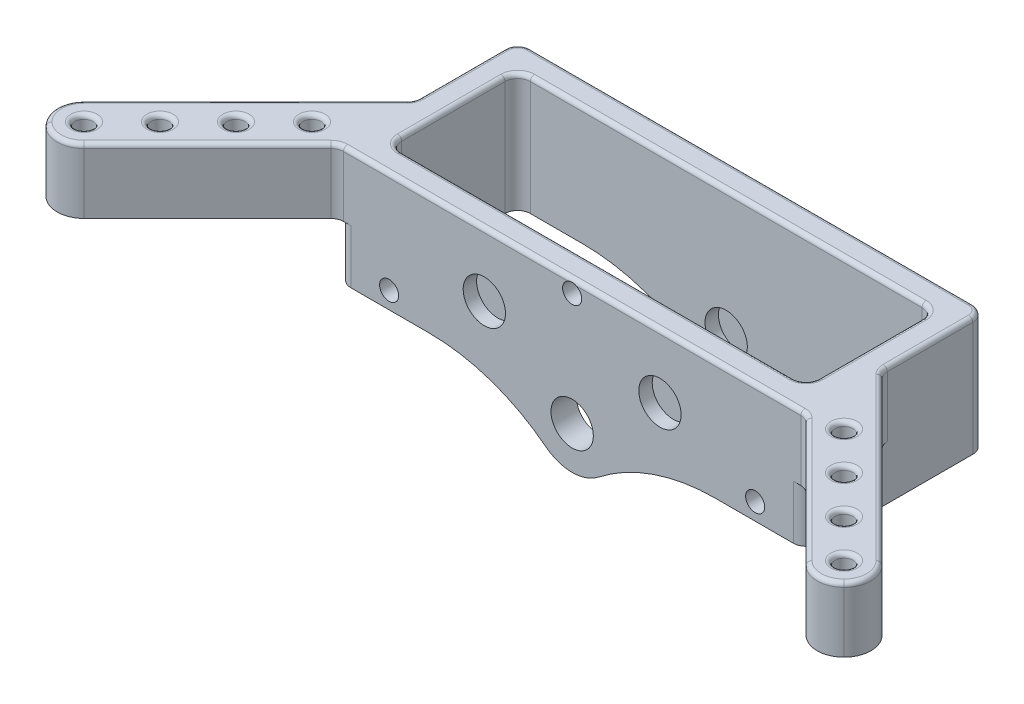
SolidWorks part; units mm, degrees
note: The reader was unsure of these and kept them because the rebuilt part matched: shared geometry of "Sketch4<3>", "Sketch4<5>", "Sketch4<6>", "Sketch4<7>", "Sketch2<4>".
ref_plane "Front Plane" through (0, 0, 0) normal (0, 0, 1) x (1, 0, 0)
ref_plane "Top Plane" through (0, 0, 0) normal (0, 1, 0) x (1, 0, 0)
ref_plane "Right Plane" through (0, 0, 0) normal (1, 0, 0) x (0, 0, -1)
sketch "Sketch2" plane through (0, 0, 0) normal (0, 1, 0) x (1, 0, 0)
  line L0 (-55.275, -21.7) -> (-89.8026, -56.2276)
  line L1 (41.275, 12.7) -> (-41.275, 12.7)
  line L2 (41.275, 12.7) -> (41.275, -12.7)
  line L3 (41.275, -12.7) -> (-41.275, -12.7)
  line L4 (-41.275, 12.7) -> (-41.275, -12.7)
  line L5 (41.275, 12.7) -> (-41.275, -12.7) construction
  line L6 (41.275, -12.7) -> (-41.275, 12.7) construction
  line L7 (-49.275, 14.7) -> (49.275, 14.7)
  line L8 (-49.275, 14.7) -> (-49.275, -15.7)
  line L9 (-49.275, -15.7) -> (49.275, -15.7)
  line L10 (49.275, 14.7) -> (49.275, -15.7)
  line L15 (-55.275, 20.7) -> (55.275, 20.7)
  line L16 (-55.275, 20.7) -> (-55.275, -21.7)
  line L17 (-55.275, -21.7) -> (55.275, -21.7)
  line L18 (55.275, 20.7) -> (55.275, -21.7)
  line L19 (-89.8026, -56.2276) -> (-98.7828, -47.2473)
  line L20 (-98.7828, -47.2473) -> (-55.275, -3.7395)
  line L21 (55.275, -21.7) -> (89.8026, -56.2276)
  line L22 (89.8026, -56.2276) -> (98.7828, -47.2473)
  line L23 (98.7828, -47.2473) -> (55.275, -3.7395)
  line L24 (-96.9319, -54.3766) -> (6.1457, 48.7009) construction
  line L25 (97.4064, -54.8512) -> (0, 42.5553) construction
  circle A0 centre (-89.8026, -47.2473) radius 2.1
  circle A1 centre (-71.842, -29.2868) radius 2.1
  circle A2 centre (71.842, -29.2868) radius 2.1
  circle A3 centre (89.8026, -47.2473) radius 2.1
  circle A4 centre (-62.8618, -20.3065) radius 2.1
  circle A5 centre (-80.8223, -38.267) radius 2.1
  circle A6 centre (62.8618, -20.3065) radius 2.1
  circle A7 centre (80.8223, -38.267) radius 2.1
  point P0 (0, 0)
  point P23 (0, 42.5553)
  dimension "D18" = 4.2
  dimension "D1" = 82.55
  dimension "D2" = 25.4
  dimension "D3" = 6
  dimension "D4" = 6
  dimension "D5" = 6
  dimension "D6" = 8
  dimension "D7" = 8
  dimension "D8" = 2
  dimension "D9" = 3
  dimension "D10" = 6
  dimension "D11" = 12.7
  dimension "D12" = 12.7
  dimension "D13" = 45
  dimension "D14" = 101.6
  dimension "D15" = 25.4
  dimension "D16" = 101.6
  dimension "D17" = 25.4
  dimension "D19" = 6.35
  dimension "D20" = 6.35
  dimension "D21" = 25.4
  dimension "D22" = 25.4
  dimension "D23" = 12.7
  dimension "D24" = 12.7
extrude "Boss-Extrude1" add sketch "Sketch2" along normal blind 28 contours L18 L15 L16 L17 L7 L10 L9 L8 | L20 L19 L0 L16 A1 A0 | L22 L23 L18 L21 A3 A2
sketch "Sketch3" plane through (0, 0, -20.7) normal (0, 0, -1) x (-1, 0, 0)
  line L2 (55.275, 28) -> (-55.275, 28) construction
  circle A0 centre (-43.25, 4) radius 2.25
  circle A1 centre (0, 25) radius 2.25
  circle A2 centre (43.25, 4) radius 2.25
  dimension "D1" = 4.5
  dimension "D2" = 21
  dimension "D3" = 3
  dimension "D4" = 86.5
  dimension "D5" = 43.25
extrude "Cut-Extrude1" cut sketch "Sketch3" against normal up to next from surface
sketch "Sketch4" plane through (0, 0, -20.7) normal (0, 0, -1) x (-1, 0, 0)
  line L0 (55.275, 0) -> (-55.275, 0) construction
  line L1 (55.275, 0) -> (-55.275, 0)
  circle A0 centre (0, 25) radius 2.25 construction
  circle A1 centre (43.25, 4) radius 2.25 construction
  circle A2 centre (-43.25, 4) radius 2.25 construction
  circle A3 centre (0, 25) radius 2.25 construction
  circle A4 centre (43.25, 4) radius 2.25 construction
  circle A5 centre (-43.25, 4) radius 2.25 construction
  circle A6 centre (-20.75, 13) radius 19.05 construction
  circle A7 centre (20.75, 13) radius 19.05 construction
  circle A8 centre (0, -1.6491) radius 6.35 construction
  circle A9 centre (-20.75, 13) radius 5
  circle A10 centre (20.75, 13) radius 5
  circle A11 centre (0, -1.6491) radius 5
  circle A12 centre (0, -1.6491) radius 10
  circle A13 centre (33.8482, -45) radius 45
  circle A14 centre (-33.8482, -45) radius 45
  circle A15 centre (0, -1.6491) radius 7.5
  line M3 (-55.275, 0) -> (55.275, 0)
  dimension "D1" = 38.1
  dimension "D2" = 38.1
  dimension "D3" = 12.7
  dimension "D8" = 10
  dimension "D9" = 10
  dimension "D10" = 10
  dimension "D11" = 20
  dimension "D12" = 90
  dimension "D13" = 15
  dimension "D4" = 9
  dimension "D5" = 9
  dimension "D6" = 22.5
  dimension "D7" = 22.5
extrude "Boss-Extrude2" add sketch "Sketch4" against normal up to surface (6 mm away) contours A14 A12 L1 | L1 A12 A11 M3 | A13 L1 A12 | L1 A11 | A15 A11 M3
extrude "Boss-Extrude3" add sketch "Sketch4<3>" against normal up to surface (6 mm away) from surface
sketch "Sketch4<3>" plane through (0, 0, -20.7) normal (0, 0, -1) x (-1, 0, 0) same geometry as "Sketch4"
extrude "Cut-Extrude3" cut sketch "Sketch4<5>" along normal blind 3.175 from surface at -6 contours L1 A11 | L1 A11 starting at face at (0, 4.9315, -14.7)
sketch "Sketch4<5>" plane through (0, 0, -20.7) normal (0, 0, -1) x (-1, 0, 0) same geometry as "Sketch4"
extrude "Cut-Extrude4" cut sketch "Sketch4<6>" against normal up to next from surface contours L1 A11 | L1 A11
sketch "Sketch4<6>" plane through (0, 0, -20.7) normal (0, 0, -1) x (-1, 0, 0) same geometry as "Sketch4"
fillet "Fillet2" radius 6.35 4 edges at (98.7828, 14, 47.2473) (89.8026, 14, 56.2276) (-89.8026, 14, 56.2276) (-98.7828, 14, 47.2473)
extrude "Cut-Extrude5" cut sketch "Sketch4<7>" along normal blind 3.175 from surface at -42.4 contours A9 | A10 starting at face at (-5, -1.6491, 21.7)
sketch "Sketch4<7>" plane through (0, 0, -20.7) normal (0, 0, -1) x (-1, 0, 0) same geometry as "Sketch4"
extrude "Cut-Extrude6" cut sketch "Sketch2<4>" along normal blind 12.7 contours L20 L19 L0 L16 A5 A4 A1 A0 | L22 L23 L18 L21 A7 A6 A3 A2
sketch "Sketch2<4>" plane through (0, 0, 0) normal (0, 1, 0) x (1, 0, 0) same geometry as "Sketch2"
fillet "Fillet1" radius 3 8 edges at (49.275, 14, 15.7) (-49.275, 14, 15.7) (55.275, 14, -20.7) (49.275, 14, -14.7) (-49.275, 14, -14.7) (-55.275, 14, -20.7) (-55.275, 6.35, 21.7) (55.275, 6.35, 21.7)
fillet "Fillet3" radius 3 4 edges at (-55.275, 20.35, 3.7395) (-55.275, 20.35, 21.7) (55.275, 20.35, 21.7) (55.275, 20.35, 3.7395)
fillet "Fillet4" radius 1 34 edges at (-48.3963, 28, 14.8213) (-49.275, 28, 0.5) (-48.3963, 28, -13.8213) (0, 28, -14.7) (48.3963, 28, -13.8213) (49.275, 28, 0.5) (48.3963, 28, 14.8213) (-55.1804, 28, 21.9284) (0, 28, 21.7) (55.1804, 28, 21.9284) (70.7331, 28, 37.1581) (89.8026, 28, 53.5973) (96.1526, 28, 47.2473) (75.2232, 28, 23.6877) (55.5034, 28, 3.6449) (55.275, 28, -7.6016) (54.3963, 28, -19.8213) (0, 28, -20.7) (-54.3963, 28, -19.8213) (-55.275, 28, -7.6016) (-55.5034, 28, 3.6449) (-75.2232, 28, 23.6877) (-96.1526, 28, 47.2473) (-89.8026, 28, 53.5973) (0, 28, 15.7) (-89.8026, 28, 49.3473) (-80.8223, 28, 40.367) (-71.842, 28, 31.3868) (-62.8618, 28, 22.4065) (62.8618, 28, 22.4065) (71.842, 28, 31.3868) (80.8223, 28, 40.367) (89.8026, 28, 49.3473) (-70.7331, 28, 37.1581)
